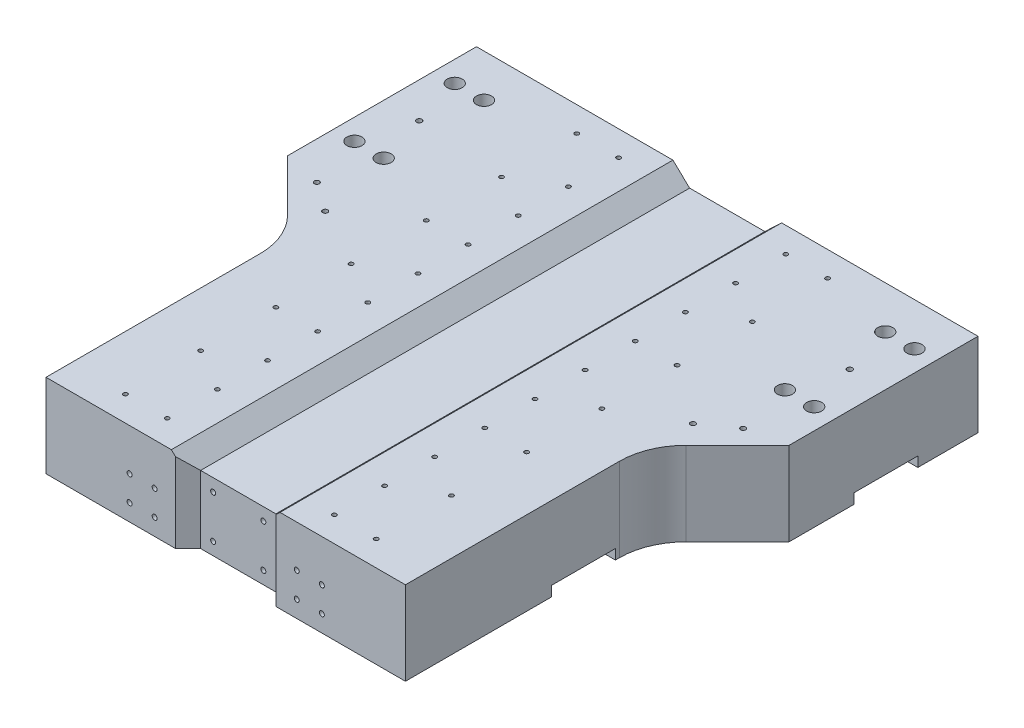
SolidWorks part; units mm, degrees
ref_plane "Front Plane" through (0, 0, 0) normal (0, 0, 1) x (1, 0, 0)
ref_plane "Top Plane" through (0, 0, 0) normal (0, 1, 0) x (1, 0, 0)
ref_plane "Right Plane" through (0, 0, 0) normal (1, 0, 0) x (0, 0, -1)
sketch "Sketch1" plane through (0, 0, 0) normal (0, 1, 0) x (1, 0, 0)
  line L1 (-300, 300) -> (300, 300)
  line L2 (-300, 300) -> (-300, -300)
  line L3 (-300, -300) -> (300, -300)
  line L4 (300, 300) -> (300, -300)
  line L5 (0, -300) -> (0, 300) construction
  line L6 (-300, 0) -> (300, 0) construction
  point P0 (0, 0)
  dimension "D1" = 600
extrude "Boss-Extrude1" add sketch "Sketch1" along normal blind 100
sketch "Sketch2" plane through (0, 100, 0) normal (0, 1, 0) x (1, 0, 0)
  line L0 (-300, -300) -> (-220, -300)
  line L9 (-300, -300) -> (300, -300) construction
  line L11 (300, -300) -> (220, -300)
  line L13 (-300, 300) -> (-300, -300) construction
  line L15 (-300, -300) -> (-300, 60)
  line L16 (300, -300) -> (300, 60)
  line L38 (-300, 60) -> (-300, 74)
  line L41 (300, 60) -> (300, 74)
  line L45 (-220, 74) -> (-300, 74)
  line L48 (220, 74) -> (300, 74)
  line L49 (-220, 74) -> (-215, 74)
  line L50 (-215, 74) -> (-215, -300)
  line L51 (-215, -300) -> (-220, -300)
  line L52 (220, 74) -> (215, 74)
  line L53 (215, 74) -> (215, -300)
  line L54 (215, -300) -> (220, -300)
extrude "Cut-Extrude1" cut sketch "Sketch2" against normal through all
chamfer "Chamfer5" distance 85 angle 45 2 edges at (-215, 50, -74) (215, 50, -74)
sketch "Sketch3" plane through (0, 0, 300) normal (0, 0, 1) x (1, 0, 0)
  line L0 (-35, 81) -> (-45, 81)
  line L2 (35, 81) -> (45, 81)
  line L4 (0, 81) -> (35, 81)
  line L8 (0, 81) -> (-35, 81)
  line L10 (-45, 100) -> (45, 100)
  line L13 (-215, 100) -> (215, 100) construction
  line L14 (-65, 100) -> (-45, 100)
  line L17 (45, 100) -> (65, 100)
  line L22 (-45, 81) -> (-65, 100)
  line L23 (45, 81) -> (65, 100)
extrude "Cut-Extrude2" cut sketch "Sketch3" against normal through all
sketch "Sketch9" plane through (0, 100, 0) normal (0, 1, 0) x (1, 0, 0)
  circle A0 centre (275, 129) radius 9.017
  circle A1 centre (240, 129) radius 9.017
  circle A3 centre (240, 249) radius 9.017
  circle A5 centre (275, 249) radius 9.017
  circle A6 centre (-275, 129) radius 9.017
  circle A7 centre (-240, 249) radius 9.017
  circle A8 centre (-275, 249) radius 9.017
  circle A11 centre (-240, 129) radius 9.017
  circle A12 centre (240, 189) radius 9.017 [skipped]
  circle A13 centre (275, 189) radius 9.017 [skipped]
  dimension "D1" = 2
  dimension "D2" = 3
extrude "Cut-Extrude5" cut sketch "Sketch9" against normal through all
sketch "Sketch12" plane through (0, 100, 0) normal (0, 1, 0) x (1, 0, 0)
  circle A40 centre (-100, -270) radius 2.5
  circle A41 centre (100, -270) radius 2.5
  circle A42 centre (100, -210) radius 2.5
  circle A43 centre (100, -150) radius 2.5
  circle A44 centre (100, -90) radius 2.5
  circle A45 centre (100, -30) radius 2.5
  circle A46 centre (100, 30) radius 2.5
  circle A47 centre (100, 90) radius 2.5
  circle A48 centre (100, 150) radius 2.5
  circle A49 centre (100, 210) radius 2.5
  circle A50 centre (100, 270) radius 2.5
  circle A61 centre (-100, -210) radius 2.5
  circle A62 centre (-100, -150) radius 2.5
  circle A63 centre (-100, -90) radius 2.5
  circle A64 centre (-100, -30) radius 2.5
  circle A65 centre (-100, 30) radius 2.5
  circle A66 centre (-100, 90) radius 2.5
  circle A67 centre (-100, 150) radius 2.5
  circle A68 centre (-100, 210) radius 2.5
  circle A69 centre (-100, 270) radius 2.5
  dimension "D1" = 2
  dimension "D2" = 10
extrude "Cut-Extrude7" cut sketch "Sketch12" against normal blind 30
sketch "Sketch14" plane through (0, 81, 0) normal (0, 1, 0) x (1, 0, 0)
  line L5 (-45, -300) -> (45, -300)
  line L6 (-45, -300) -> (-45, -285)
  line L11 (45, -285) -> (45, -300)
  line L15 (-45, -285) -> (45, -285)
extrude "Cut-Extrude8" cut sketch "Sketch14" against normal through all
chamfer "Chamfer3" distance 15 angle 45 2 edges at (45, 40.5, 300) (-45, 40.5, 300)
sketch "Sketch15" plane through (-300, 0, 0) normal (-1, 0, 0) x (0, 0, 1)
  line L8 (125, -0.7) -> (125, 12)
  line L9 (125, 12) -> (48.8, 12)
  line L10 (48.8, 12) -> (48.8, -0.7)
  line L11 (48.8, -0.7) -> (125, -0.7)
  line L12 (-228, 12) -> (-228, -0.7)
  line L13 (-228, -0.7) -> (-151.8, -0.7)
  line L14 (-151.8, -0.7) -> (-151.8, 12)
  line L15 (-151.8, 12) -> (-228, 12)
extrude "Cut-Extrude9" cut sketch "Sketch15" against normal through all
sketch "Sketch22" plane through (0, 0, -300) normal (0, 0, -1) x (-1, 0, 0)
  line L0 (-45, 81) -> (-45, 0)
  line L1 (-300, 0) -> (300, 0) construction
  line L2 (-45, 0) -> (45, 0)
  line L3 (45, 0) -> (45, 81)
  line L4 (45, 81) -> (-45, 81)
sketch "Sketch17" plane through (0, 0, 285) normal (0, 0, 1) x (1, 0, 0)
  line L8 (30, 66) -> (-30, 66)
  line L9 (-30, 66) -> (-30, 15)
  line L10 (-30, 15) -> (30, 15)
  line L11 (30, 15) -> (30, 66)
  line L12 (30, 66) -> (-30, 66)
  line L13 (-30, 66) -> (-30, 15)
  line L14 (-30, 15) -> (30, 15)
  line L15 (30, 15) -> (30, 66)
  dimension "D1" = 15
sketch "Sketch19" plane through (0, 0, -300) normal (0, 0, -1) x (-1, 0, 0)
  line L0 (30, 66) -> (30, 15) construction
  line L1 (30, 15) -> (-30, 15) construction
  line L2 (-30, 15) -> (-30, 66) construction
  line L3 (-30, 66) -> (30, 66) construction
  line L4 (30, 66) -> (30, 15)
  line L5 (30, 15) -> (-30, 15)
  line L6 (-30, 15) -> (-30, 66)
  line L7 (-30, 66) -> (30, 66)
sketch "Sketch20" plane through (0, 0, 300) normal (0, 0, 1) x (1, 0, 0)
  line L2 (85, 100) -> (85, 50)
  line L3 (-85, 0) -> (-85, 20)
  line L4 (-215, 100) -> (-65, 100) construction
  line L5 (-85, 100) -> (-85, 50)
  line L6 (115, 100) -> (115, 50)
  line L7 (-115, 100) -> (-115, 50)
  line L8 (0, 34.1921) -> (0, 91.6213)
  line L9 (-215, 0) -> (-60, 0) construction
  line L10 (-115, 0) -> (-115, 20)
  line L11 (85, 0) -> (85, 20)
  line L12 (115, 0) -> (115, 20)
sketch "Sketch21" plane through (0, 0, -300) normal (0, 0, -1) x (-1, 0, 0)
  line L4 (-115, 100) -> (-115, 80)
  line L5 (-85, 100) -> (-85, 80)
  line L6 (85, 100) -> (85, 80)
  line L7 (115, 100) -> (115, 80)
  line L8 (115, 0) -> (115, 20) construction
  line L9 (85, 0) -> (85, 20) construction
  line L10 (-85, 0) -> (-85, 20) construction
  line L11 (-115, 0) -> (-115, 20) construction
  line L12 (115, 0) -> (115, 20)
  line L13 (85, 0) -> (85, 20)
  line L14 (-85, 0) -> (-85, 20)
  line L15 (-115, 0) -> (-115, 20)
hole_wizard "Ø6.0mm Dowel Hole1" positions "3DSketch2" profile "Sketch18" hole size "Ø6.0" standard "ANSI Metric"
sketch3d "3DSketch2"
  point P0 (-30, 66, 285)
  point P3 (30, 66, 285)
  point P6 (30, 15, 285)
  point P9 (-30, 15, 285)
  point P13 (30, 66, -300)
  point P16 (-30, 66, -300)
  point P19 (-30, 15, -300)
  point P22 (30, 15, -300)
  point P26 (-85, 50, 300)
  point P29 (-115, 50, 300)
  point P32 (85, 50, 300)
  point P35 (115, 50, 300)
  point P38 (-115, 80, -300)
  point P41 (-85, 80, -300)
  point P44 (85, 80, -300)
  point P47 (115, 80, -300)
  point P50 (-115, 20, 300)
  point P53 (-85, 20, 300)
  point P56 (85, 20, 300)
  point P59 (115, 20, 300)
  point P62 (-115, 20, -300)
  point P65 (-85, 20, -300)
  point P68 (85, 20, -300)
  point P71 (115, 20, -300)
sketch "Sketch18" plane through (-30, 66, 285) normal (1, 0, 0) x (0, -1, 0)
  line L0 (0, 0) -> (0, 31.8026)
  line L1 (0, 31.8026) -> (3, 30)
  line L2 (3, 30) -> (3, 0)
  line L5 (3, 0) -> (0, 0)
  line L10 (0, 31.8026) -> (-3, 30) construction
  line L11 (0, -6.35) -> (0, 107.95) construction
  dimension "Hole Dia." = 6
  dimension "Hole Depth" = 30
  dimension "Drill Angle" = 118
sketch "Sketch23" plane through (0, 100, 0) normal (0, 1, 0) x (1, 0, 0)
  circle A0 centre (-257.5, 189) radius 3.175
  circle A1 centre (257.5, 189) radius 3.175
extrude "Cut-Extrude10" cut sketch "Sketch23" against normal through all
sketch "Sketch24" plane through (0, 100, 0) normal (0, 1, 0) x (1, 0, 0)
  line L0 (210, 74) -> (300, 74) construction
  line L1 (210, 74) -> (300, 74)
  line L2 (210, 74) -> (210, 4)
  line L3 (210, 39) -> (220, 39)
  line L4 (255, 74) -> (255, 64)
  line L5 (0, 0) -> (0, -82.778)
  circle A0 centre (255, 64) radius 3
  circle A1 centre (220, 39) radius 3
  circle A2 centre (-220, 39) radius 3
  circle A3 centre (-255, 64) radius 3
extrude "Cut-Extrude11" cut sketch "Sketch24" against normal blind 20 contours A3 | A2 | A0 | A1
fillet "Fillet1" radius 80 2 edges at (215, 50, 11) (-215, 50, 11)
sketch "Sketch25" plane through (0, 100, 0) normal (0, 1, 0) x (1, 0, 0)
  line L0 (0, 0) -> (0, -72.5445)
  circle A4 centre (150, 270) radius 2.5
  circle A5 centre (150, 90) radius 2.5
  circle A6 centre (150, -90) radius 2.5
  circle A7 centre (150, -270) radius 2.5
  circle A8 centre (-150, -270) radius 2.5
  circle A9 centre (-150, -90) radius 2.5
  circle A10 centre (-150, 90) radius 2.5
  circle A11 centre (-150, 270) radius 2.5
  circle A12 centre (-150, 180) radius 2.5
  circle A13 centre (150, 180) radius 2.5
  circle A14 centre (150, 0) radius 2.5
  circle A15 centre (-150, 0) radius 2.5
  circle A16 centre (150, -180) radius 2.5
  circle A17 centre (-150, -180) radius 2.5
hole_wizard "Ø5.0mm Dowel Hole1" positions "Sketch26" profile "Sketch27" hole size "Ø5.0" standard "ANSI Metric"
sketch "Sketch26" plane through (0, 100, 0) normal (0, 1, 0) x (1, 0, 0)
  point P0 (-150, 270)
  point P3 (150, 270)
  point P6 (-150, 90)
  point P9 (150, 90)
  point P12 (-150, -90)
  point P15 (150, -90)
  point P18 (-150, -270)
  point P21 (150, -270)
  point P25 (150, 180)
  point P28 (-150, 180)
  point P31 (-150, 0)
  point P34 (150, 0)
  point P37 (150, -180)
  point P40 (-150, -180)
sketch "Sketch27" plane through (-150, 100, -270) normal (1, 0, 0) x (0, 0, 1)
  line L0 (0, 0) -> (0, 30)
  line L1 (0, 30) -> (2.5, 28.4978)
  line L2 (2.5, 28.4978) -> (2.5, 0)
  line L5 (2.5, 0) -> (0, 0)
  line L10 (0, 30) -> (-2.5, 28.4978) construction
  line L11 (0, -6.35) -> (0, 107.95) construction
  dimension "Hole Dia." = 5
  dimension "Hole Depth" = 30
  dimension "Drill Angle" = 118
